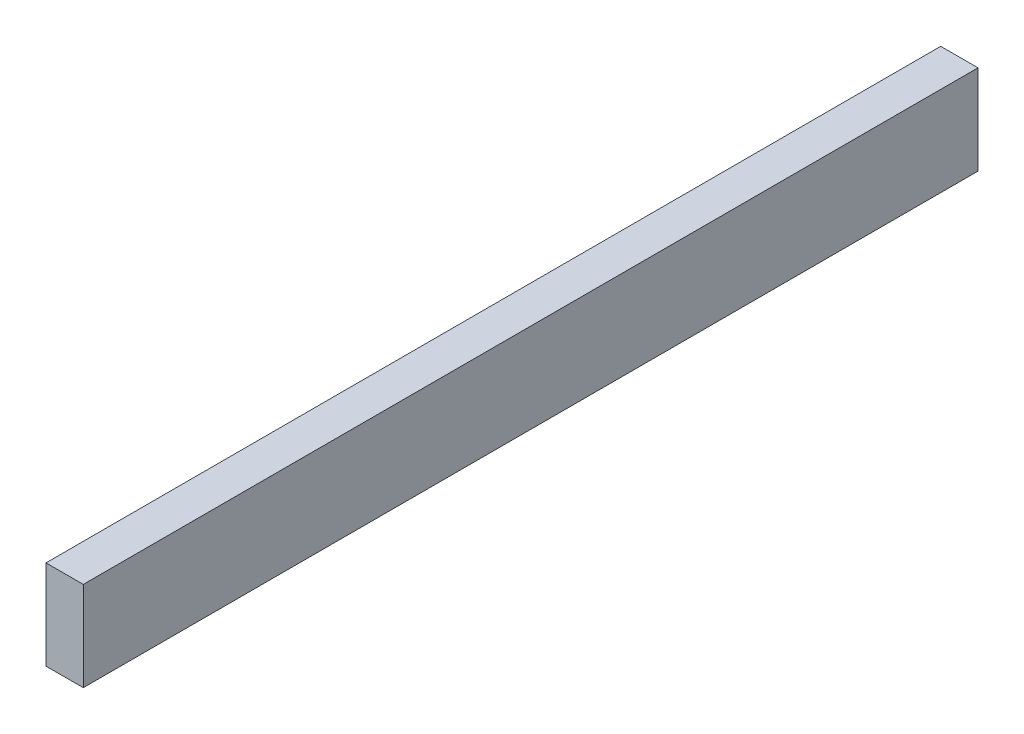
SolidWorks part; units mm, degrees
ref_plane "Front" through (0, 0, 0) normal (0, 0, 1) x (1, 0, 0)
ref_plane "Top" through (0, 0, 0) normal (0, 1, 0) x (1, 0, 0)
ref_plane "Right" through (0, 0, 0) normal (1, 0, 0) x (0, 0, -1)
sketch "Skizze1" plane through (0, 0, 0) normal (1, 0, 0) x (0, 0, -1)
  line L1 (0, 0) -> (120, 0)
  line L2 (0, 0) -> (0, 12)
  line L3 (0, 12) -> (120, 12)
  line L4 (120, 0) -> (120, 12)
  dimension "D1" = 12
  dimension "D2" = 120
extrude "Aufsatz-Linear austragen1" add sketch "Skizze1" along normal blind 5
